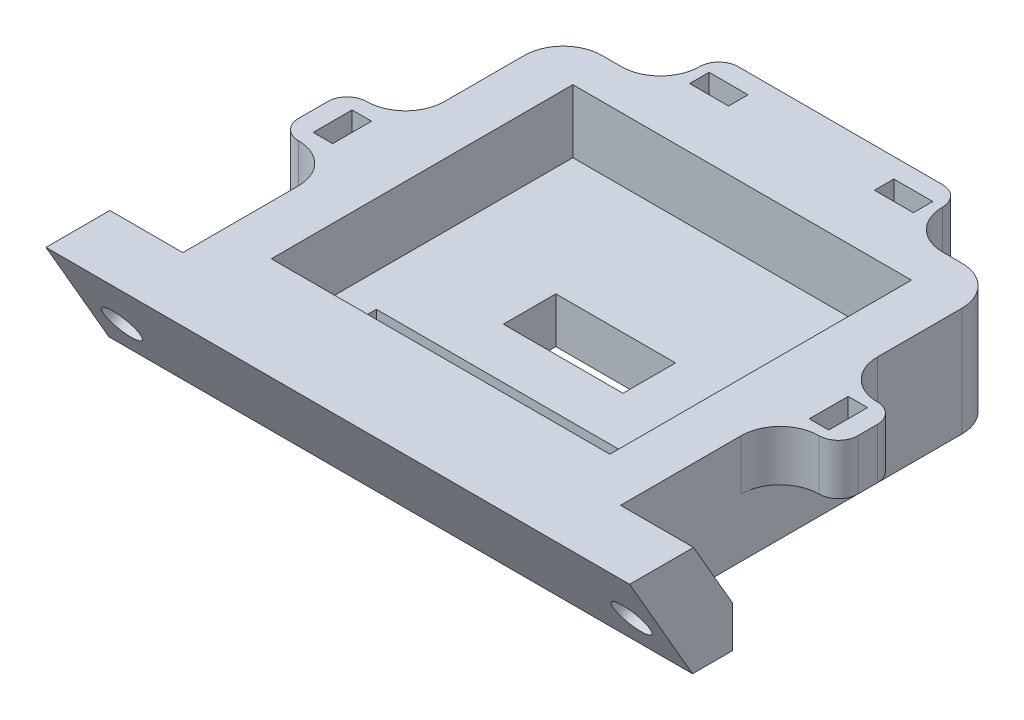
SolidWorks part; units mm, degrees
ref_plane "Front Plane" through (0, 0, 0) normal (0, 0, 1) x (1, 0, 0)
ref_plane "Top Plane" through (0, 0, 0) normal (0, 1, 0) x (1, 0, 0)
ref_plane "Right Plane" through (0, 0, 0) normal (1, 0, 0) x (0, 0, -1)
sketch "Sketch2" plane through (0, 0, 0) normal (0, 1, 0) x (1, 0, 0)
  line L1 (0, 0) -> (57.15, 0)
  line L2 (0, 0) -> (0, 49.784)
  line L3 (0, 49.784) -> (57.15, 49.784)
  line L4 (57.15, 0) -> (57.15, 49.784)
  dimension "D1" = 57.15
  dimension "D2" = 49.784
extrude "Boss-Extrude1" add sketch "Sketch2" along normal blind 14.224
sketch "Sketch3" plane through (0, 14.224, 0) normal (0, 1, 0) x (1, 0, 0)
  line L0 (0, 49.784) -> (0, 0) construction
  line L1 (6.477, 44.577) -> (50.673, 44.577)
  line L2 (6.477, 44.577) -> (6.477, 5.207)
  line L3 (6.477, 5.207) -> (50.673, 5.207)
  line L4 (50.673, 44.577) -> (50.673, 5.207)
  line L5 (57.15, 49.784) -> (0, 49.784) construction
  point P6 (0, 24.892)
  point P7 (6.477, 24.892)
  point P10 (28.575, 49.784)
  point P11 (28.575, 44.577)
  dimension "D1" = 44.196
  dimension "D2" = 39.37
extrude "Cut-Extrude1" cut sketch "Sketch3" against normal blind 8.255
sketch "Sketch4" plane through (0, 5.969, 0) normal (0, 1, 0) x (1, 0, 0)
  line L1 (10.795, 14.605) -> (46.355, 14.605)
  line L2 (10.795, 14.605) -> (10.795, 10.414)
  line L3 (10.795, 10.414) -> (46.355, 10.414)
  line L4 (46.355, 14.605) -> (46.355, 10.414)
  line L6 (6.477, 5.207) -> (50.673, 5.207) construction
  line L7 (50.673, 44.577) -> (6.477, 44.577) construction
  line L8 (20.7645, 28.067) -> (36.3855, 28.067)
  line L9 (20.7645, 28.067) -> (20.7645, 21.209)
  line L10 (20.7645, 21.209) -> (36.3855, 21.209)
  line L11 (36.3855, 28.067) -> (36.3855, 21.209)
  line L12 (6.477, 5.207) -> (50.673, 5.207) construction
  point P6 (28.575, 5.207)
  point P7 (28.575, 10.414)
  point P10 (28.575, 21.209)
  point P15 (28.575, 14.605)
  dimension "D1" = 35.56
  dimension "D3" = 9.398
  dimension "D4" = 4.191
  dimension "D5" = 15.621
  dimension "D6" = 6.858
  dimension "D7" = 16.51
extrude "Cut-Extrude2" cut sketch "Sketch4" against normal blind 8.255
sketch "Sketch5" plane through (0, 14.224, 0) normal (0, 1, 0) x (1, 0, 0)
  line L0 (0, 49.784) -> (0, 0) construction
  line L5 (57.15, 49.784) -> (0, 49.784) construction
  line L6 (0, 29.21) -> (-7.62, 29.21)
  line L7 (0, 29.21) -> (0, 20.32)
  line L8 (0, 20.32) -> (-7.62, 20.32)
  line L9 (-7.62, 29.21) -> (-7.62, 20.32)
  line L10 (12.7, 49.784) -> (36.83, 49.784)
  line L11 (12.7, 49.784) -> (12.7, 57.404)
  line L12 (12.7, 57.404) -> (36.83, 57.404)
  line L15 (36.83, 49.784) -> (44.45, 49.784)
  line L17 (36.83, 57.404) -> (44.45, 57.404)
  line L18 (44.45, 49.784) -> (44.45, 57.404)
  line L23 (57.15, 0) -> (57.15, 49.784) construction
  line L24 (57.15, 28.575) -> (64.77, 28.575)
  line L25 (57.15, 28.575) -> (57.15, 20.955)
  line L26 (57.15, 20.955) -> (64.77, 20.955)
  line L27 (64.77, 28.575) -> (64.77, 20.955)
  line L29 (0, 0) -> (57.15, 0) construction
  point P0 (36.068, 49.784)
  point P1 (0, 24.765)
  point P2 (57.15, 24.765)
  dimension "D1" = 8.89
  dimension "D2" = 7.62
  dimension "D3" = 29.21
  dimension "D4" = 12.7
  dimension "D5" = 12.7
extrude "Boss-Extrude2" add sketch "Sketch5" against normal blind 6.604
sketch "Sketch6" plane through (0, 14.224, 0) normal (0, 1, 0) x (1, 0, 0)
  line L1 (-5.08, 27.305) -> (-2.54, 27.305)
  line L2 (-5.08, 27.305) -> (-5.08, 22.225)
  line L3 (-5.08, 22.225) -> (-2.54, 22.225)
  line L4 (-2.54, 27.305) -> (-2.54, 22.225)
  line L13 (59.69, 27.305) -> (62.23, 27.305)
  line L14 (59.69, 27.305) -> (59.69, 22.225)
  line L15 (59.69, 22.225) -> (62.23, 22.225)
  line L16 (62.23, 27.305) -> (62.23, 22.225)
  line L18 (-7.62, 29.21) -> (-7.62, 20.32) construction
  line L19 (64.77, 20.955) -> (64.77, 28.575) construction
  line L20 (44.45, 57.404) -> (12.7, 57.404) construction
  line L22 (13.97, 54.864) -> (19.05, 54.864)
  line L23 (13.97, 54.864) -> (13.97, 52.324)
  line L24 (13.97, 52.324) -> (19.05, 52.324)
  line L25 (19.05, 54.864) -> (19.05, 52.324)
  line L26 (0, 49.784) -> (0, 29.21) construction
  line L30 (57.15, 28.575) -> (57.15, 49.784) construction
  line L31 (38.1, 54.864) -> (43.18, 54.864)
  line L32 (38.1, 54.864) -> (38.1, 52.324)
  line L33 (38.1, 52.324) -> (43.18, 52.324)
  line L34 (43.18, 54.864) -> (43.18, 52.324)
  point P28 (-7.62, 24.765)
  point P29 (-5.08, 24.765)
  point P30 (-2.54, 24.765)
  point P31 (59.69, 24.765)
  dimension "D1" = 5.08
  dimension "D2" = 2.54
  dimension "D3" = 5.08
  dimension "D4" = 2.54
  dimension "D5" = 5.08
  dimension "D6" = 2.54
  dimension "D7" = 2.54
  dimension "D8" = 2.54
  dimension "D9" = 2.54
  dimension "D10" = 2.54
  dimension "D11" = 2.54
  dimension "D12" = 5.08
  dimension "D13" = 13.97
  dimension "D14" = 13.97
extrude "Cut-Extrude3" cut sketch "Sketch6" against normal blind 6.604
fillet "Fillet1" radius 5.08 4 edges at (0, 7.112, -49.784) (0, 7.112, 0) (57.15, 7.112, 0) (57.15, 7.112, -49.784)
fillet "Fillet2" radius 2.54 6 edges at (64.77, 10.922, -20.955) (64.77, 10.922, -28.575) (-7.62, 10.922, -20.32) (-7.62, 10.922, -29.21) (44.45, 10.922, -57.404) (12.7, 10.922, -57.404)
sketch "Sketch7" plane through (0, 0, 0) normal (0, 0, 1) x (1, 0, 0)
  line L0 (-9.525, 14.224) -> (66.675, 14.224)
  line L1 (66.675, 14.224) -> (66.675, 0)
  line L2 (66.675, 0) -> (-9.525, 0)
  line L3 (-9.525, 0) -> (-9.525, 14.224)
  line L4 (5.08, 14.224) -> (52.07, 14.224) construction
  line L5 (5.08, 0) -> (52.07, 0) construction
  circle A0 centre (-5.461, 7.112) radius 2.3813
  circle A1 centre (62.611, 7.112) radius 2.3813
  point P9 (28.575, 0)
  point P10 (28.575, 0)
  point P18 (-9.525, 7.112)
  dimension "D1" = 4.7625
  dimension "D2" = 4.064
  dimension "D3" = 4.064
  dimension "D4" = 76.2
extrude "Boss-Extrude3" add sketch "Sketch7" against normal up to surface (5.207 mm away) up to face at (28.575, 10.0965, -5.207)
sketch "Sketch8" plane through (-9.525, 0, 0) normal (-1, 0, 0) x (0, 0, 1)
  line L0 (-5.207, 0) -> (-5.207, 14.224)
  line L1 (-5.207, 14.224) -> (8.2122, 14.224)
  line L2 (8.2122, 14.224) -> (0, 0)
  line L3 (0, 0) -> (-5.207, 0)
  dimension "D1" = 60
extrude "Boss-Extrude4" add sketch "Sketch8" against normal up to surface (76.2 mm away) up to face at (66.675, 7.112, -2.6035)
sketch "Sketch9" plane through (0, 0, 0) normal (0, -0.5, 0.866) x (1, 0, 0)
  line L0 (-9.525, 0) -> (-9.525, 16.4245) construction
  line L1 (66.675, 0) -> (66.675, 16.4245) construction
  line L2 (66.675, 16.4245) -> (-9.525, 16.4245) construction
  circle A0 centre (-4.699, 6.2645) radius 2.413
  circle A1 centre (61.849, 6.2645) radius 2.413
  point P8 (0, 0)
  point P10 (0, 0)
  dimension "D1" = 4.826
  dimension "D2" = 4.826
  dimension "D3" = 4.826
  dimension "D4" = 10.16
extrude "Cut-Extrude4" cut sketch "Sketch9" against normal blind 25.4
chamfer "Chamfer1" distance 5.08 angle 60 1 edges at (61.9125, 14.224, -5.207) first distance on face at (28.575, 14.224, -24.892)
chamfer "Chamfer2" distance 5.08 angle 60 1 edges at (-4.7625, 14.224, -5.207) first distance on face at (28.575, 14.224, -24.892)
fillet "Fillet3" radius 5.08 2 edges at (44.45, 10.922, -49.784) (12.7, 10.922, -49.784)
fillet "Fillet4" radius 5.08 4 edges at (57.15, 10.922, -20.955) (57.15, 10.922, -28.575) (0, 10.922, -29.21) (0, 10.922, -20.32)
